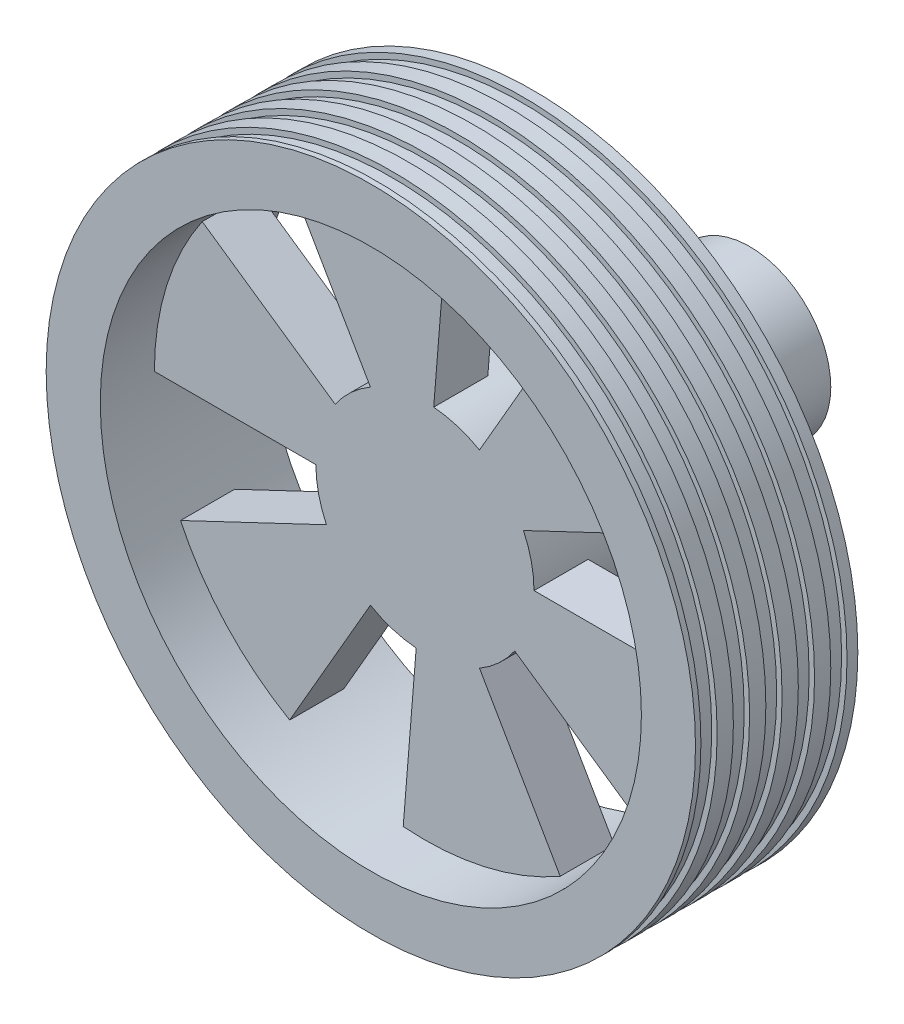
SolidWorks part; units mm, degrees
ref_plane "Front Plane" through (0, 0, 0) normal (0, 0, 1) x (1, 0, 0)
ref_plane "Top Plane" through (0, 0, 0) normal (0, 1, 0) x (1, 0, 0)
ref_plane "Right Plane" through (0, 0, 0) normal (1, 0, 0) x (0, 0, -1)
sketch "Sketch1" plane through (0, 0, 0) normal (0, 0, 1) x (1, 0, 0)
  circle A0 centre (0, 0) radius 30
  dimension "D1" = 60
extrude "Boss-Extrude1" add sketch "Sketch1" along normal blind 15
sketch "Sketch2" plane through (0, 0, 0) normal (0, 0, 1) x (1, 0, 0)
  circle A0 centre (0, 0) radius 1
  circle A1 centre (0, 0) radius 7.5
  dimension "D1" = 2
  dimension "D2" = 15
extrude "Boss-Extrude2" add sketch "Sketch2" against normal blind 20
sketch "Sketch4" plane through (0, 0, -20) normal (0, 0, -1) x (-1, 0, 0)
  circle A0 centre (0, 0) radius 3.175
  dimension "D1" = 6.35
extrude "Cut-Extrude1" cut sketch "Sketch4" against normal blind 1.6
sketch "Sketch5" plane through (0, 0, 0) normal (1, 0, 0) x (0, 0, -1)
  line L0 (0, 55) -> (0, -55) construction
  line L1 (0, 7.5) -> (2, 7.5)
  line L2 (0, 7.5) -> (0, 10.0764)
  line L3 (0, 10.0764) -> (2, 10.0764)
  line L4 (2, 7.5) -> (2, 10.0764)
  line L5 (20, 7.5) -> (0, 7.5) construction
  line L6 (2, 10.0764) -> (12, 10.0764) construction
  line L7 (12, 10.0764) -> (12, 4.3117) construction
  line L9 (12, 7.5) -> (13.5, 7.5)
  line L10 (12, 7.5) -> (12, 6.5)
  line L11 (12, 6.5) -> (13.5, 6.5)
  line L12 (13.5, 7.5) -> (13.5, 6.5)
  dimension "D1" = 10
  dimension "D2" = 2
  dimension "D3" = 1
  dimension "D4" = 1.5
ref_axis "Axis1" through (0, 0, -21.75) along (0, 0, 1)
revolve "Revolve2" add sketch "Sketch5" angle 360 about axis through (0, 0, -21.75) along (0, 0, 1)
revolve "Cut-Revolve1" cut sketch "Sketch5<4>" angle 360 about axis through (0, 0, -21.75) along (0, 0, 1)
sketch "Sketch5<4>" plane through (0, 0, 0) normal (1, 0, 0) x (0, 0, -1) same geometry as "Sketch5"
sketch "Sketch6" plane through (0, 0, 0) normal (0, 0, -1) x (-1, 0, 0)
  circle A0 centre (0, 0) radius 25
  circle A1 centre (0, 0) radius 10.0764
  dimension "D1" = 50
extrude "Cut-Extrude2" cut sketch "Sketch6" against normal blind 5
sketch "Sketch7" plane through (0, 0, 15) normal (0, 0, 1) x (1, 0, 0)
  circle A0 centre (0, 0) radius 25
  dimension "D1" = 50
extrude "Cut-Extrude3" cut sketch "Sketch7" against normal blind 5
sketch "Sketch8" plane through (0, 0, 5) normal (0, 0, -1) x (-1, 0, 0)
  line L0 (-10.0764, 0) -> (-25, 0)
  line L1 (55, 0) -> (-55, 0) construction
  line L2 (-22.5843, 10.7214) -> (-9.1028, 4.3213)
  line L3 (-2.0071, 24.9193) -> (-0.809, 10.0439)
  line L4 (-5.0382, 8.7264) -> (-12.5, 21.6506)
  line L5 (20.5772, 14.1979) -> (8.2938, 5.7226)
  line L6 (5.0382, 8.7264) -> (12.5, 21.6506)
  line L7 (22.5843, -10.7214) -> (9.1028, -4.3213)
  line L8 (10.0764, 0) -> (25, 0)
  line L9 (2.0071, -24.9193) -> (0.809, -10.0439)
  line L10 (5.0382, -8.7264) -> (12.5, -21.6506)
  line L11 (-20.5772, -14.1979) -> (-8.2938, -5.7226)
  line L12 (-5.0382, -8.7264) -> (-12.5, -21.6506)
  circle A0 centre (0, 0) radius 10.0764 construction
  circle A1 centre (0, 0) radius 25 construction
  circle A2 centre (0, 0) radius 10.0764 construction
  arc A3 (-22.5843, 10.7214) -> (-25, 0) centre (0, 0) ccw
  arc A4 (-9.1028, 4.3213) -> (-10.0764, 0) centre (0, 0) ccw
  arc A5 (-0.809, 10.0439) -> (-5.0382, 8.7264) centre (0, 0) ccw
  arc A6 (-2.0071, 24.9193) -> (-12.5, 21.6506) centre (0, 0) ccw
  arc A7 (8.2938, 5.7226) -> (5.0382, 8.7264) centre (0, 0) ccw
  arc A8 (20.5772, 14.1979) -> (12.5, 21.6506) centre (0, 0) ccw
  arc A9 (9.1028, -4.3213) -> (10.0764, 0) centre (0, 0) ccw
  arc A10 (22.5843, -10.7214) -> (25, 0) centre (0, 0) ccw
  arc A11 (0.809, -10.0439) -> (5.0382, -8.7264) centre (0, 0) ccw
  arc A12 (2.0071, -24.9193) -> (12.5, -21.6506) centre (0, 0) ccw
  arc A13 (-8.2938, -5.7226) -> (-5.0382, -8.7264) centre (0, 0) ccw
  arc A14 (-20.5772, -14.1979) -> (-12.5, -21.6506) centre (0, 0) ccw
  point P37 (0, 0)
  dimension "D1" = 6
extrude "Cut-Extrude4" cut sketch "Sketch8" against normal blind 5
sketch "Sketch9" plane through (0, 0, 0) normal (1, 0, 0) x (0, 0, -1)
  line L0 (-2.5, 30) -> (-2.5, 29.5)
  line L1 (0, 30) -> (-15, 30) construction
  line L2 (-2.5, 29.5) -> (-1, 29.5)
  line L3 (-1, 29.5) -> (-1, 30)
  line L4 (-1, 30) -> (-2.5, 30)
  line L5 (0, 33) -> (0, -33) construction
  line L6 (-4, 30) -> (-5.5, 30)
  line L7 (-5.5, 29.5) -> (-4, 29.5)
  line L8 (-5.5, 30) -> (-5.5, 29.5)
  line L9 (-4, 29.5) -> (-4, 30)
  line L10 (-7, 30) -> (-8.5, 30)
  line L11 (-8.5, 29.5) -> (-7, 29.5)
  line L12 (-8.5, 30) -> (-8.5, 29.5)
  line L13 (-7, 29.5) -> (-7, 30)
  line L14 (-10, 30) -> (-11.5, 30)
  line L15 (-11.5, 29.5) -> (-10, 29.5)
  line L16 (-11.5, 30) -> (-11.5, 29.5)
  line L17 (-10, 29.5) -> (-10, 30)
  line L18 (-13, 30) -> (-14.5, 30)
  line L19 (-14.5, 29.5) -> (-13, 29.5)
  line L20 (-14.5, 30) -> (-14.5, 29.5)
  line L21 (-13, 29.5) -> (-13, 30)
  dimension "D1" = 1
  dimension "D2" = 1.5
  dimension "D3" = 0.5
  dimension "D4" = 5
revolve "Cut-Revolve2" cut sketch "Sketch9" angle 360 about axis through (0, 0, -21.75) along (0, 0, 1)
